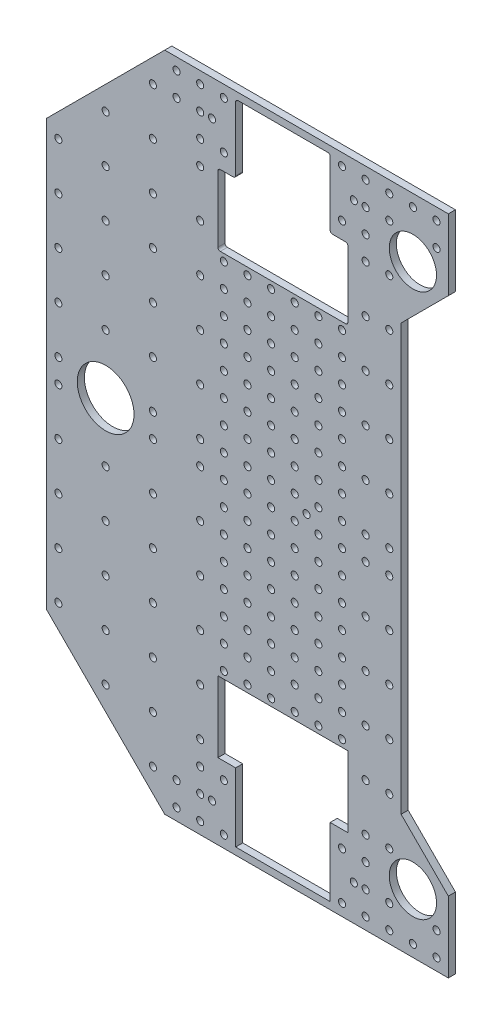
SolidWorks part; units mm, degrees
ref_plane "Front Plane" through (0, 0, 0) normal (0, 0, 1) x (1, 0, 0)
ref_plane "Top Plane" through (0, 0, 0) normal (0, 1, 0) x (1, 0, 0)
ref_plane "Right Plane" through (0, 0, 0) normal (1, 0, 0) x (0, 0, -1)
ref_axis "Axis1" through (-88.99, 0, 0) along (1, 0, 0)
ref_axis "Axis3" through (0, -55, 0) along (0, 1, 0)
sketch "Sketch1" plane through (0, 0, 0) normal (0, 0, 1) x (1, 0, 0)
  line L0 (-110, 90) -> (-110, -90)
  line L1 (-110, -90) -> (-60, -140)
  line L2 (-60, -140) -> (60, -140)
  line L3 (60, -140) -> (60, -110)
  line L4 (60, -110) -> (40, -90)
  line L5 (40, -90) -> (40, 90)
  line L6 (40, 90) -> (60, 110)
  line L7 (60, 110) -> (60, 140)
  line L8 (60, 140) -> (-60, 140)
  line L9 (-60, 140) -> (-110, 90)
  line L10 (-88.99, 0) -> (88.99, 0) construction
  circle A0 centre (78, 0) radius 38 construction
  circle A1 centre (78, -76) radius 38 construction
  circle A2 centre (78, 76) radius 38 construction
  circle A3 centre (0, 0) radius 1.5
  point P2 (-110, 0)
  point P14 (-41.3479, 0)
  point P21 (0, 140)
  dimension "D15" = 76
  dimension "D18" = 3
  dimension "D1" = 180
  dimension "D2" = 170
  dimension "D3" = 50
  dimension "D4" = 50
  dimension "D5" = 135
  dimension "D6" = 110
  dimension "D7" = 20
  dimension "D8" = 180
  dimension "D9" = 120
  dimension "D10" = 28.2843
  dimension "D11" = 70.7107
  dimension "D12" = 50
  dimension "D13" = 30
  dimension "D14" = 30
  dimension "D16" = 120
  dimension "D17" = 280
extrude "Main" add sketch "Sketch1" along normal blind 3
sketch "Sketch2" plane through (0, 0, 3) normal (0, 0, 1) x (1, 0, 0)
  line L0 (-37.5, 108) -> (-37.5, 78)
  line L1 (-37.5, 78) -> (17.5, 78)
  line L2 (17.5, 78) -> (17.5, 108)
  line L3 (17.5, 108) -> (10, 108)
  line L4 (10, 108) -> (10, 137)
  line L5 (10, 137) -> (-30, 137)
  line L6 (-30, 137) -> (-30, 108)
  line L7 (-30, 108) -> (-37.5, 108)
  line L8 (0, -55) -> (0, 55) construction
  line L9 (-88.99, 0) -> (88.99, 0) construction
  line L10 (60, 140) -> (-60, 140) construction
  point P9 (-10, 78)
  dimension "D1" = 55
  dimension "D2" = 78
  dimension "D3" = 40
  dimension "D4" = 29
  dimension "D5" = 30
  dimension "D6" = 3
  dimension "D7" = 10
extrude "MotorCoderLeftHole" cut sketch "Sketch2" against normal through all
fillet "Fillet1" radius 1 8 edges at (-30, 137, 1.5) (10, 108, 1.5) (17.5, 108, 1.5) (10, 137, 1.5) (17.5, 78, 1.5) (-37.5, 78, 1.5) (-37.5, 108, 1.5) (-30, 108, 1.5)
sketch "Sketch7" plane through (0, 0, 3) normal (0, 0, 1) x (1, 0, 0)
  line L0 (-88.99, 0) -> (88.99, 0) construction
  line L1 (-15, 75) -> (-5, 75) construction
  line L2 (-36.5, 78) -> (16.5, 78) construction
  circle A0 centre (-15, 75) radius 1.5
  circle A1 centre (-25, 75) radius 1.5
  circle A2 centre (-5, 75) radius 1.5
  circle A3 centre (-35, 75) radius 1.5
  circle A4 centre (5, 75) radius 1.5
  circle A5 centre (15, 75) radius 1.5
  point P5 (-10, 78)
  point P6 (-10, 75)
  dimension "D1" = 3
  dimension "D2" = 75
  dimension "D3" = 10
  dimension "D4" = 10
  dimension "D5" = 10
  dimension "D6" = 10
  dimension "D7" = 10
extrude "MotorFixHoles" cut sketch "Sketch7" against normal through all
pattern_linear "MotorFixHoleLPattern" count 8 spacing 10 along (0, -1, 0) of "MotorFixHoles"
sketch "Sketch8" plane through (0, 0, 3) normal (0, 0, 1) x (1, 0, 0)
  line L0 (60, 140) -> (-60, 140) construction
  line L1 (-45, 135) -> (-35, 115) construction
  line L2 (-35, 135) -> (-45, 115) construction
  line L3 (0, -55) -> (0, 55) construction
  line L4 (-49, 135.7238) -> (-49, 114.2762) construction
  line L5 (-31, 114.2762) -> (-31, 135.7238) construction
  line L6 (-49, 125) -> (-31, 125) construction
  circle A0 centre (-40, 125) radius 1.5
  circle A1 centre (-45, 115) radius 1.5
  circle A2 centre (-35, 115) radius 1.5
  circle A3 centre (-45, 135) radius 1.5
  circle A4 centre (-35, 135) radius 1.5
  arc A5 (-49, 114.2762) -> (-31, 114.2762) centre (-40, 125) ccw construction
  arc A6 (-31, 135.7238) -> (-49, 135.7238) centre (-40, 125) ccw construction
  point P20 (-40, 125)
  point P24 (-40, 139)
  point P25 (-40, 111)
  dimension "D1" = 3
  dimension "D6" = 3
  dimension "D7" = 14
  dimension "D2" = 20
  dimension "D3" = 10
  dimension "D4" = 5
  dimension "D5" = 40
  dimension "D8" = 28
  dimension "D9" = 18
extrude "LinearBallFix" cut sketch "Sketch8" against normal through all
pattern_linear "LinearBallFix2" count 2 spacing 60 along (1, 0, 0) of "LinearBallFix"
sketch "Sketch4" plane through (0, 0, 3) normal (0, 0, 1) x (1, 0, 0)
  line L0 (-88.99, 0) -> (88.99, 0) construction
  circle A0 centre (-105, 5) radius 1.5
  dimension "D1" = 3
  dimension "D2" = 5
  dimension "D3" = 5
extrude "BottomLeftHole" cut sketch "Sketch4" against normal through all
pattern_linear "BottomLeftHoleLPattern" count 9 spacing 20 along (0, 1, 0) of "BottomLeftHole"
sketch "Sketch5" plane through (0, 0, 3) normal (0, 0, 1) x (1, 0, 0)
  line L1 (60, 110) -> (60, 140) construction
  circle A0 centre (-55, 135) radius 1.5
  circle A3 centre (35, 135) radius 1.5
  circle A4 centre (55, 135) radius 1.5
  dimension "D3" = 3
  dimension "D8" = 5
  dimension "D9" = 3
  dimension "D10" = 3
  dimension "D1" = 5
  dimension "D2" = 5
  dimension "D4" = 20
extrude "BottomLeftHole2" cut sketch "Sketch5" against normal through all
pattern_linear "BottomToTopPattern" count 4 spacing 20 along (1, 0, 0) of "BottomLeftHoleLPattern"
pattern_linear "LPattern3" count 2 spacing 10 along (0, -1, 0) of "BottomLeftHole2"
pattern_linear "FrontHoles" count 2 spacing 140 along (1, 0, 0) of "BottomLeftHoleLPattern"
sketch "Sketch9" plane through (0, 0, 3) normal (0, 0, 1) x (1, 0, 0)
  line L0 (-85, 5) -> (-85, 118.3839) construction
  line L1 (-65, 5) -> (-65, 125.7809) construction
  line L2 (-45, 5) -> (-45, 111.0784) construction
  line L3 (-105, 5) -> (-55, 135) construction
  line L4 (60, 140) -> (-60, 140) construction
  circle A0 centre (-85, 25) radius 1.5
  circle A1 centre (-65, 25) radius 1.5
  circle A2 centre (-45, 25) radius 1.5
  circle A3 centre (-65, 45) radius 1.5
  circle A4 centre (35, 105) radius 1.5
  circle A5 centre (35, 125) radius 1.5 construction
  circle A6 centre (45, 135) radius 1.5
  circle A7 centre (35, 135) radius 1.5 construction
  point P25 (35, 125)
  dimension "D1" = 3
  dimension "D4" = 20
  dimension "D5" = 10
  dimension "D2" = 20
  dimension "D3" = 20
  dimension "D6" = 5
extrude "Cut-Extrude2" cut sketch "Sketch9" against normal through all
pattern_linear "LPattern6" count 2 spacing 130 along (1, 0, 0) of "BottomLeftHoleLPattern"
mirror "Mirror1" about plane through (0, 0, 0) normal (0, 1, 0) of "LPattern6", "LPattern3", "FrontHoles", "MotorCoderLeftHole", "BottomLeftHole", "BottomLeftHoleLPattern", "BottomLeftHole2", "BottomToTopPattern", "MotorFixHoles", "MotorFixHoleLPattern", "LinearBallFix", "LinearBallFix2", "Cut-Extrude2"
sketch "Sketch3" plane through (0, 0, 3) normal (0, 0, 1) x (1, 0, 0)
  line L0 (-88.99, 0) -> (88.99, 0) construction
  line L1 (-110, 90) -> (-110, -90) construction
  line L3 (60, 110) -> (60, 140) construction
  line L5 (60, 140) -> (-60, 140) construction
  circle A0 centre (-85, 0) radius 12
  circle A1 centre (45, 115) radius 10
  circle A2 centre (45, -115) radius 10
  point P10 (45, 0)
  point P26 (45, 0)
  dimension "D1" = 24
  dimension "D3" = 20
  dimension "D6" = 230
  dimension "D2" = 25
  dimension "D4" = 15
  dimension "D5" = 25
extrude "BigHoles" cut sketch "Sketch3" against normal through all
